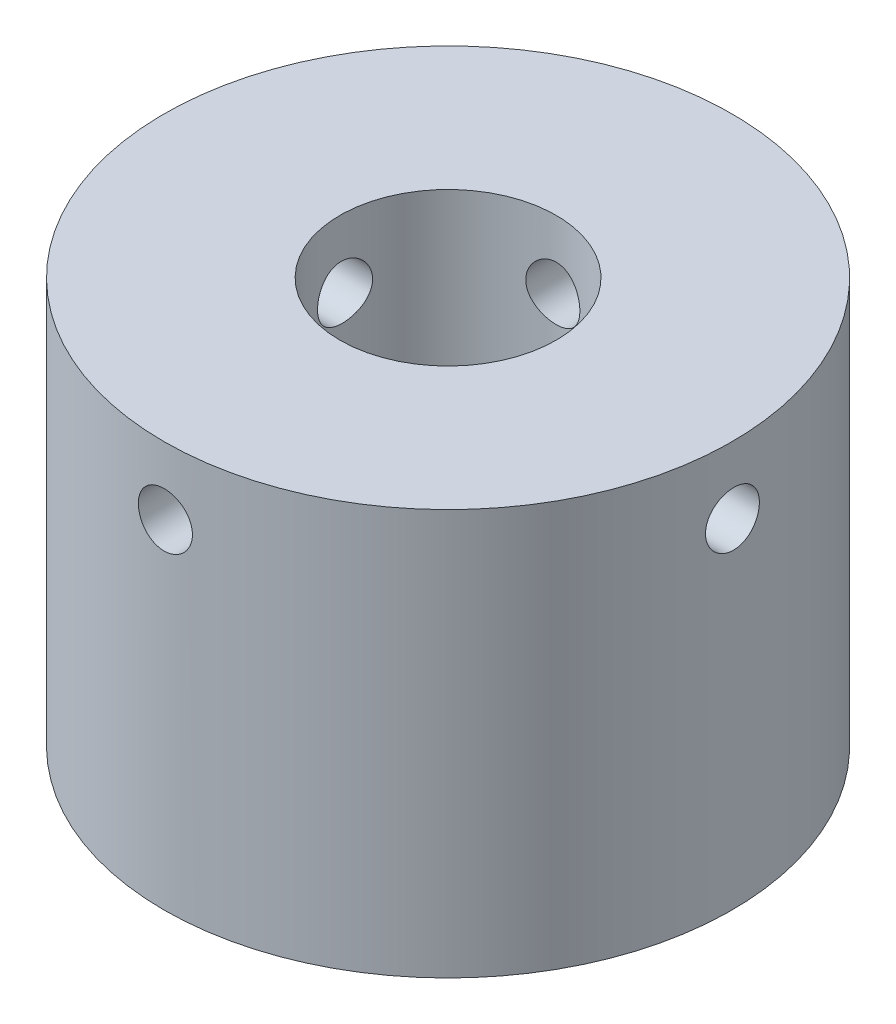
SolidWorks part; units mm, degrees
ref_plane "Alzado" through (0, 0, 0) normal (0, 0, 1) x (1, 0, 0)
ref_plane "Planta" through (0, 0, 0) normal (0, 1, 0) x (1, 0, 0)
ref_plane "Vista lateral" through (0, 0, 0) normal (1, 0, 0) x (0, 0, -1)
sketch "Croquis1" plane through (0, 0, 0) normal (0, 1, 0) x (1, 0, 0)
  circle A0 centre (0, 0) radius 4
  circle A1 centre (0, 0) radius 10.5
  dimension "D1" = 8
  dimension "D2" = 21
extrude "Saliente-Extruir1" add sketch "Croquis1" along normal blind 15
sketch "Croquis2" plane through (0, 0, 0) normal (0, 0, 1) x (1, 0, 0)
  line L0 (4, 15) -> (-4, 15) construction
  circle A0 centre (0, 12.5) radius 1
  dimension "D1" = 2
  dimension "D2" = 2.5
extrude "Cortar-Extruir1" cut sketch "Croquis2" against normal blind 15 and the other way blind 15
sketch "Croquis3" plane through (0, 0, 0) normal (1, 0, 0) x (0, 0, -1)
  line L0 (4, 13.5) -> (4, 11.5) construction
  line L1 (4, 11.5) -> (4, 12.5) construction
  line L2 (4, 12.5) -> (-3.873, 12.5) construction
  circle A0 centre (0.0635, 12.5) radius 1.002
  spline S0 degree 2 poles (-4, 13.5) (-3.75, 12.5) (-4, 11.5) knots 0 0 0 1 1 1 weights 0.003 0.004 0.005 construction
  dimension "D1" = 2.004
extrude "Cortar-Extruir2" cut sketch "Croquis3" against normal blind 15 and the other way blind 15
